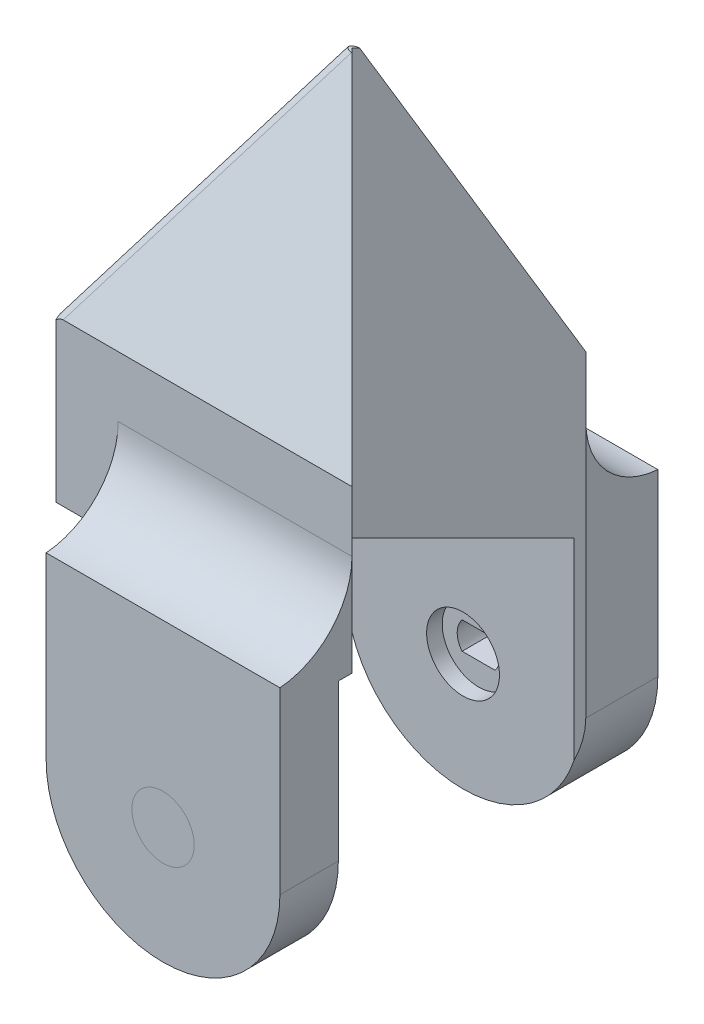
SolidWorks part; units mm, degrees
ref_plane "Front Plane" through (0, 0, 0) normal (0, 0, 1) x (1, 0, 0)
ref_plane "Top Plane" through (0, 0, 0) normal (0, 1, 0) x (1, 0, 0)
ref_plane "Right Plane" through (0, 0, 0) normal (1, 0, 0) x (0, 0, -1)
sketch "Sketch2" plane through (0, 0, 0) normal (0, 0, 1) x (1, 0, 0)
  line L0 (-7.55, 18.2411) -> (-7.55, 14.75)
  line L1 (-7.55, 14.75) -> (7.55, 14.75)
  line L2 (7.55, 14.75) -> (7.55, 18.2411)
  line L3 (7.55, 18.2411) -> (9.25, 18.2411)
  line L4 (9.25, 18.2411) -> (9.25, 21.1603)
  line L5 (-7.55, 18.2411) -> (-9.25, 18.2411)
  line L6 (-9.25, 18.2411) -> (-9.25, 21.1603)
  line L7 (-14.7095, 40) -> (-23, 40)
  line L8 (-23, 40) -> (-23, 0)
  line L10 (14.7095, 40) -> (23, 40)
  line L11 (23, 40) -> (23, 0)
  line L13 (-23, 0) -> (23, 0)
  arc A0 (14.7095, 40) -> (-14.7095, 40) centre (0, 40) ccw
  arc A4 (9.25, 21.1603) -> (-9.25, 21.1603) centre (0, 32) ccw
  point P6 (0, 14.75)
  point P15 (0, 0)
  dimension "D1" = 8.2905
  dimension "D12" = 3.4911
  dimension "D16" = 14.25
  dimension "D17" = 14.7095
  dimension "D2" = 8.2905
  dimension "D3" = 25.25
  dimension "D4" = 40
  dimension "D5" = 0
  dimension "D6" = 0
  dimension "D7" = 46
  dimension "D9" = 2.9191
  dimension "D10" = 1.7
  dimension "D11" = 1.7
  dimension "D13" = 15.1
  dimension "D14" = 2.9191
  dimension "D15" = 3.4911
extrude "Boss-Extrude1" add sketch "Sketch2" along normal blind 20.95
sketch "Sketch3" plane through (0, 0, 0) normal (0, 0, 1) x (1, 0, 0)
  line L7 (-14.7095, 40) -> (-23, 40)
  line L8 (-23, 40) -> (-23, 0)
  line L9 (14.7095, 40) -> (23, 40)
  line L10 (23, 40) -> (23, 0)
  line L11 (-23, 0) -> (23, 0)
  line L12 (23, 40) -> (14.7095, 40) construction
  line L13 (-23, 40) -> (-23, 0) construction
  line L17 (-23, 0) -> (23, 0) construction
  line L19 (23, 0) -> (23, 40) construction
  arc A0 (14.7095, 40) -> (-14.7095, 40) centre (0, 40) ccw
  arc A1 (14.7095, 40) -> (-14.7095, 40) centre (0, 40) ccw construction
  dimension "D1" = 0
extrude "Boss-Extrude2" add sketch "Sketch3" against normal blind 9.05
sketch "Sketch6" plane through (0, 0, 20.95) normal (0, 0, 1) x (1, 0, 0)
  line L0 (-14.7095, 40) -> (-23, 40) construction
  line L1 (-23, 40) -> (-23, 0) construction
  line L2 (23, 40) -> (14.7095, 40) construction
  line L3 (23, 0) -> (23, 40) construction
  circle A0 centre (-17.5, 32) radius 2
  circle A1 centre (17.5, 32) radius 2
  dimension "D1" = 8
  dimension "D2" = 5.5
  dimension "D3" = 4
  dimension "D4" = 8
  dimension "D5" = 5.5
  dimension "D6" = 4
extrude "Cut-Extrude2" cut sketch "Sketch6" against normal blind 10
sketch "Sketch7" plane through (0, 0, 20.95) normal (0, 0, 1) x (1, 0, 0)
  line L0 (-17.5, 32) -> (17.5, 32) construction
  line L3 (-17.5, 35.75) -> (17.5, 35.75)
  line L4 (-17.5, 28.25) -> (17.5, 28.25)
  arc A2 (-17.5, 35.75) -> (-17.5, 28.25) centre (-17.5, 32) ccw
  arc A3 (17.5, 28.25) -> (17.5, 35.75) centre (17.5, 32) ccw
  circle A4 centre (-17.5, 32) radius 2 construction
  circle A5 centre (-17.5, 32) radius 2 construction
  circle A6 centre (17.5, 32) radius 2 construction
  point P2 (0, 32)
  dimension "D2" = 7.5
  dimension "D3" = 1.75
  dimension "D4" = 1.75
  dimension "D1" = 3.75
extrude "Cut-Extrude3" cut sketch "Sketch7" against normal blind 2.75
sketch "Sketch8" plane through (0, 0, 20.95) normal (0, 0, 1) x (1, 0, 0)
  line L0 (-14.7095, 40) -> (-23, 40) construction
  line L1 (-14.7095, 40) -> (-23, 40)
  line L2 (-14.7095, 40) -> (-14.7095, 36.75)
  line L3 (-14.7095, 36.75) -> (-23, 36.75)
  line L4 (-23, 40) -> (-23, 36.75)
  line L5 (14.7095, 40) -> (23, 40)
  line L6 (14.7095, 40) -> (14.7095, 36.75)
  line L7 (14.7095, 36.75) -> (23, 36.75)
  line L8 (23, 40) -> (23, 36.75)
  line L9 (-23, 40) -> (-23, 0) construction
  line L10 (-13.7477, 35.75) -> (-17.5, 35.75) construction
  line L11 (17.5, 35.75) -> (13.7477, 35.75) construction
  line L12 (23, 0) -> (23, 40) construction
  line L13 (23, 40) -> (14.7095, 40) construction
  dimension "D2" = 1
  dimension "D3" = 1
extrude "Cut-Extrude4" cut sketch "Sketch8" along normal through all both and the other way through all
sketch "Sketch11" plane through (0, 0, -9.05) normal (0, 0, -1) x (-1, 0, 0)
  circle A0 centre (0, 40) radius 11.15
  arc A1 (14.7095, 40) -> (-14.7095, 40) centre (0, 40) ccw construction
  dimension "D1" = 22.3
extrude "Bearing Hole" cut sketch "Sketch11" against normal blind 7.3
sketch "Sketch12" plane through (0, 0, 0) normal (0, -1, 0) x (1, 0, 0)
  line L0 (-23, -9.05) -> (23, -9.05) construction
  line L1 (-23, -9.05) -> (23, -9.05)
  line L2 (-23, -9.05) -> (-23, 20.95)
  line L3 (-23, 20.95) -> (23, 20.95)
  line L4 (23, -9.05) -> (23, 20.95)
  line L5 (-23, 20.95) -> (23, 20.95) construction
  line L7 (-23, 20.95) -> (-23, -9.05) construction
  point P4 (0, -9.05)
  dimension "D1" = 0
  dimension "D2" = 0
  dimension "D3" = 0
  dimension "D4" = 0
extrude "Boss-Extrude3" add sketch "Sketch12" along normal blind 0.0001
sketch "Sketch13" plane through (0, 0, 20.95) normal (0, 0, 1) x (1, 0, 0)
  line L0 (-15, -0.0001) -> (15, -0.0001)
  line L1 (23, -0.0001) -> (-23, -0.0001) construction
  line L2 (15, -0.0001) -> (15, -20.0001)
  line L3 (-15, -0.0001) -> (-15, -20.0001)
  line L4 (0, -26.675) -> (0, 26.675) construction
  arc A0 (-15, -20.0001) -> (15, -20.0001) centre (0, -20.0001) ccw
  point P7 (0, -0.0001)
  dimension "D1" = 15
  dimension "D2" = 0
  dimension "D3" = 20
extrude "Boss-Extrude4" add sketch "Sketch13" along normal blind 9.25 and the other way blind 39.25
sketch "Sketch14" plane through (-15, 0, 0) normal (-1, 0, 0) x (0, 0, 1)
  line L0 (20.95, -0.0001) -> (30.2, -0.0001) construction
  line L1 (22.7, -35.0001) -> (-8.3, -35.0001)
  line L2 (22.7, -35.0001) -> (22.7, -0.0001)
  line L3 (22.7, -0.0001) -> (-8.3, -0.0001)
  line L4 (-8.3, -35.0001) -> (-8.3, -0.0001)
  line L6 (-18.3, -35.0001) -> (30.2, -35.0001) construction
  line L7 (30.2, -0.0001) -> (30.2, -20.0001) construction
  dimension "D1" = 31
  dimension "D2" = 0
  dimension "D3" = 0
  dimension "D4" = 7.5
extrude "Cut-Extrude5" cut sketch "Sketch14" against normal through all
sketch "Sketch15" plane through (0, 0, 30.2) normal (0, 0, 1) x (1, 0, 0)
  circle A0 centre (0, -20.0001) radius 4
  arc A2 (-15, -20.0001) -> (15, -20.0001) centre (0, -20.0001) ccw construction
  dimension "D1" = 8
extrude "Cut-Extrude6" cut sketch "Sketch15" against normal through all
sketch "Sketch17" plane through (0, 0, -18.3) normal (0, 0, -1) x (-1, 0, 0)
  line L0 (-2.1213, -18.2501) -> (2.1213, -18.2501)
  line L1 (-2.1213, -21.7501) -> (2.1213, -21.7501)
  arc A0 (-2.1213, -18.2501) -> (-2.1213, -21.7501) centre (0, -20.0001) ccw
  arc A1 (2.1213, -18.2501) -> (2.1213, -21.7501) centre (0, -20.0001) cw
  circle A2 centre (0, -20.0001) radius 6.1696
  circle A4 centre (0, -20.0001) radius 4 construction
  dimension "D3" = 2.75
  dimension "D4" = 2.75
  dimension "D1" = 4.2426
  dimension "D2" = 4.2426
extrude "Boss-Extrude5" add sketch "Sketch17" against normal up to surface (10 mm away) up to face at (-4, -20.0001, -8.3)
sketch "Sketch18" plane through (0, 0, 30.2) normal (0, 0, 1) x (1, 0, 0)
  circle A0 centre (0, -20.0001) radius 4
  circle A1 centre (0, -20.0001) radius 4 construction
  dimension "D1" = 8
extrude "Boss-Extrude6" add sketch "Sketch18" against normal offset from surface (14 mm away) 6.5 separate body up to face at (4, -20.0001, 22.7) offset beyond the face yes
sketch "Sketch19" plane through (0, 0, -8.3) normal (0, 0, 1) x (1, 0, 0)
  circle A0 centre (0, -20.0001) radius 4.675
  circle A1 centre (0, -20.0001) radius 4 construction
  dimension "D1" = 9.35
extrude "Cut-Extrude7" cut sketch "Sketch19" against normal blind 2
sketch "Sketch20" plane through (0, 0, 20.95) normal (0, 0, 1) x (1, 0, 0)
  line L1 (-15, -0.0001) -> (15, -0.0001)
  line L2 (-15, -0.0001) -> (-15, 2.9999)
  line L3 (-15, 2.9999) -> (15, 2.9999)
  line L4 (15, -0.0001) -> (15, 2.9999)
  dimension "D1" = 3
extrude "Boss-Extrude7" add sketch "Sketch20" along normal up to surface (9.25 mm away) and the other way up to surface (39.25 mm away) up to face at (4, -20.0001, 30.2) other way up to face at (0, -13.7501, -18.3)
fillet "Fillet1" radius 10 2 edges at (0, 2.9999, 20.95) (0, 2.9999, -9.05)
sketch "Sketch22" plane through (0, -0.0001, 0) normal (0, -1, 0) x (1, 0, 0)
  line L1 (15, 20.95) -> (32.2207, 20.95)
  line L2 (15, 20.95) -> (15, -9.05)
  line L3 (15, -9.05) -> (32.2207, -9.05)
  line L4 (32.2207, 20.95) -> (32.2207, -9.05)
extrude "Cut-Extrude8" cut sketch "Sketch22" against normal through all
sketch "Sketch25" plane through (0, 0, -9.05) normal (0, 0, -1) x (-1, 0, 0)
  line L0 (23, 36.75) -> (23, -0.0001) construction
  line L1 (23, 14.4524) -> (-15.7795, 14.4524)
  line L2 (23, 14.4524) -> (23, 59.0118)
  line L3 (23, 59.0118) -> (-15.7795, 59.0118)
  line L4 (-15.7795, 14.4524) -> (-15.7795, 59.0118)
extrude "Cut-Extrude10" cut sketch "Sketch25" against normal through all
ref_plane "Plane1" through (15, 14.4524, 20.95) normal (0, 0, -1) x (-1, 0, 0)
ref_plane "Plane2" through (0, 0, 5.95) normal (0, 0, -1) x (-1, 0, 0)
ref_axis "Axis1" through (0, 66.5781, 5.95) along (0, -1, 0)
sketch "Sketch38" plane through (0, 14.4524, 0) normal (0, 1, 0) x (1, 0, 0)
  line L0 (15, 9.05) -> (0, -5.95)
  line L1 (0, -5.95) -> (15, -20.95)
  line L2 (15, -20.95) -> (-23, -20.95)
  line L3 (-23, -20.95) -> (-23, 9.05)
  line L4 (-23, 9.05) -> (15, 9.05)
extrude "Boss-Extrude9" add sketch "Sketch38" along normal blind 40
sketch "Sketch39" plane through (-23, 0, 0) normal (-1, 0, 0) x (0, 0, 1)
  line L0 (6.45, 54.4524) -> (20.95, 54.4524)
  line L1 (20.95, 54.4524) -> (20.95, 20.7289)
  line L2 (20.95, 54.4524) -> (20.95, -0.0001) construction
  line L3 (20.95, 20.7289) -> (6.45, 54.4524)
  line L4 (-9.05, 54.4524) -> (20.95, 54.4524) construction
  line L5 (5.95, 66.5781) -> (5.95, -3.1705) construction
  line L6 (-9.05, 54.4524) -> (-9.05, 20.7289)
  line L7 (-9.05, 54.4524) -> (-9.05, -0.0001) construction
  line L8 (-9.05, 20.7289) -> (5.45, 54.4524)
  line L9 (5.45, 54.4524) -> (-9.05, 54.4524)
  dimension "D1" = 0.5
  dimension "D2" = 0.5
extrude "Cut-Extrude11" cut sketch "Sketch39" against normal through all
sketch "Sketch40" plane through (0, 0, 20.95) normal (0, 0, 1) x (1, 0, 0)
  line L0 (-23, 54.4524) -> (-0.5, 54.4524)
  line L1 (0.5, 54.4524) -> (-23, 54.4524) construction
  line L2 (-0.5, 54.4524) -> (-23, 20.7289)
  line L3 (-23, 20.7289) -> (-23, 54.4524)
  line L4 (0, 66.5781) -> (0, -3.1705) construction
  dimension "D1" = 0.5
extrude "Cut-Extrude12" cut sketch "Sketch40" against normal through all
sketch "Sketch41" plane through (0, 14.4524, 0) normal (0, 1, 0) x (1, 0, 0)
  line L0 (15, 9.05) -> (0, -5.95)
  line L1 (0, -5.95) -> (15, -20.95)
  line L2 (15, -20.95) -> (15, 9.05)
extrude "Cut-Extrude13" cut sketch "Sketch41" against normal through all
fillet "Fillet2" radius 1 2 edges at (-11.75, 37.5906, 13.7) (-11.75, 37.5906, -1.8)
